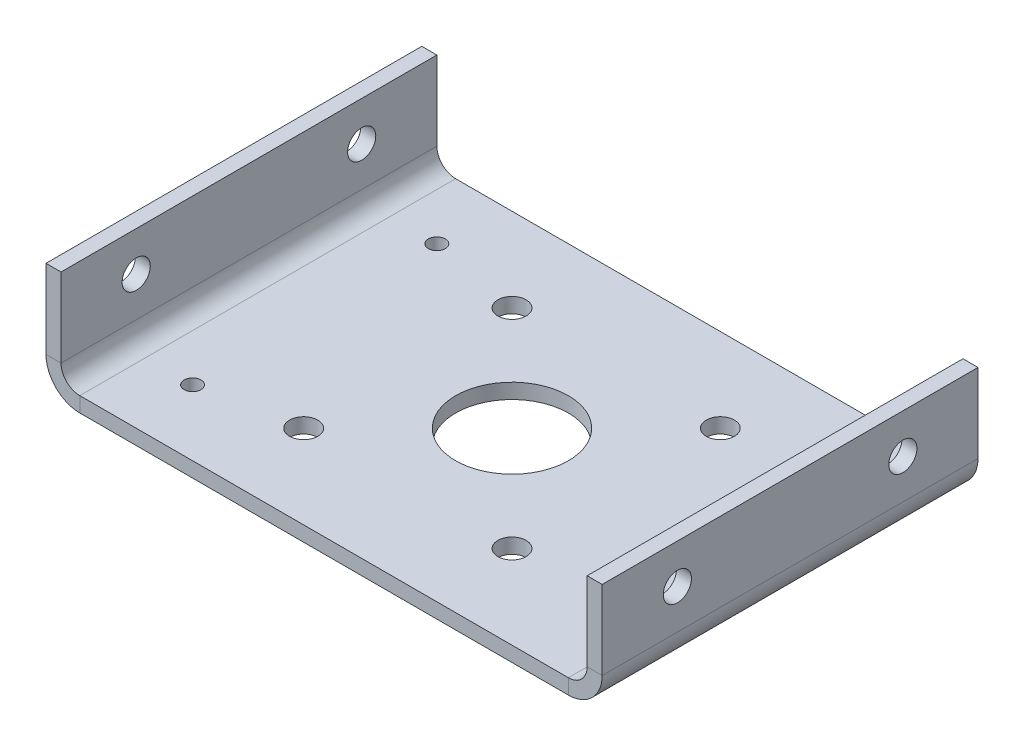
SolidWorks part; units mm, degrees
note: The reader was unsure of these and kept them because the rebuilt part matched: flange length of "Edge-Flange1".
material "Plain Carbon Steel"
ref_plane "Front Plane" through (0, 0, 0) normal (0, 0, 1) x (1, 0, 0)
ref_plane "Top Plane" through (0, 0, 0) normal (0, 1, 0) x (1, 0, 0)
ref_plane "Right Plane" through (0, 0, 0) normal (1, 0, 0) x (0, 0, -1)
sketch "Sketch1" plane through (0, 0, 0) normal (0, 1, 0) x (1, 0, 0)
  line L1 (-148, -100) -> (148, -100)
  line L2 (-148, -100) -> (-148, 100)
  line L3 (-148, 100) -> (148, 100)
  line L4 (148, -100) -> (148, 100)
  line L5 (-148, -100) -> (148, 100) construction
  line L6 (-148, 100) -> (148, -100) construction
  point P0 (0, 0)
  dimension "D1" = 296
  dimension "D2" = 200
base flange "Base-Flange1" sketch "Sketch1" thickness 8 reverse thickness direction no parameters "D1"=3
edge flange "Edge-Flange1" sketch "Sketch10" flange profiles "Sketch10", "Sketch11" flange angle 90 flange length 60 flange position material inside bend radius 10 thickness 8 relief rectangular parameters "D6"=10, "D8"=1
sketch "Sketch10" plane through (-148, 0, 0) normal (-1, 0, 0) x (0, 0, 1)
  line L0 (-100, 0) -> (100, 0) construction
  line L1 (-100, 0) -> (100, 0)
  line L2 (-100, 0) -> (-100, 52)
  line L3 (-100, 52) -> (100, 52)
  line L4 (100, 52) -> (100, 0)
sketch "Sketch11" plane through (148, 0, 0) normal (1, 0, 0) x (0, 0, -1)
  line L0 (-100, 0) -> (100, 0) construction
  line L1 (-100, 0) -> (100, 0)
  line L2 (-100, 0) -> (-100, 52)
  line L3 (-100, 52) -> (100, 52)
  line L4 (100, 52) -> (100, 0)
bend "EdgeBend1" bend radius 10 bend angle 90 parameters "D5"=1
bend "EdgeBend2" bend radius 10 bend angle 90 parameters "D5"=2
sketch "Sketch12" plane through (0, -8, 0) normal (0, -1, 0) x (-1, 0, 0)
  circle A0 centre (0, 0) radius 30
  dimension "D1" = 60
extrude "Cut-Extrude1" cut sketch "Sketch12" against normal blind 10
sketch "Sketch13" plane through (0, -8, 0) normal (0, -1, 0) x (-1, 0, 0)
  line L3 (-55.4372, -55.4372) -> (55.4372, -55.4372) construction
  line L4 (-55.4372, -55.4372) -> (-55.4372, 55.4372) construction
  line L5 (-55.4372, 55.4372) -> (55.4372, 55.4372) construction
  line L6 (55.4372, -55.4372) -> (55.4372, 55.4372) construction
  line L7 (-55.4372, -55.4372) -> (55.4372, 55.4372) construction
  line L8 (-55.4372, 55.4372) -> (55.4372, -55.4372) construction
  circle A0 centre (55.4372, -55.4372) radius 7.5
  point P4 (0, 0)
  dimension "D1" = 15
  dimension "D3" = 78.4
extrude "Cut-Extrude2" cut sketch "Sketch13" against normal blind 10
mirror "Mirror4" about plane through (0, 0, 0) normal (1, 0, 0) of "Cut-Extrude2"
sketch "Sketch15" plane through (-148, 0, 0) normal (-1, 0, 0) x (0, 0, 1)
  line L2 (-100, 0) -> (-100, 52) construction
  line L3 (100, 10) -> (-100, 10) construction
  circle A0 centre (-60, 31) radius 7.5
  dimension "D1" = 15
  dimension "D2" = 40
  dimension "D3" = 21
extrude "Cut-Extrude3" cut sketch "Sketch15" against normal through all
sketch "Sketch16" plane through (0, -8, 0) normal (0, -1, 0) x (-1, 0, 0)
  line L1 (130, -100) -> (130, 100) construction
  line L2 (-130, 100) -> (130, 100) construction
  circle A0 centre (105, 65) radius 4.5
  dimension "D1" = 25
  dimension "D2" = 35
  dimension "D3" = 9
extrude "Cut-Extrude4" cut sketch "Sketch16" against normal blind 10
mirror "Mirror5" about plane through (0, 0, 0) normal (0, 0, 1) of "Cut-Extrude3", "Mirror4", "Cut-Extrude4", "Cut-Extrude2"
sketch "Bend-Lines1" [suppressed] plane through (0, 0, 0) normal (0, 1, 0) x (1, 0, 0)
sketch "Bounding-Box1" [suppressed] plane through (0, 0, 0) normal (0, 1, 0) x (1, 0, 0)
sheet metal parameters "Sheet-Metal1" thickness 8 parameters "D1"=3
flat pattern "Flat-Pattern1" [suppressed]
sketch "Bend-Lines2" plane through (0, 0, 0) normal (0, 1, 0) x (1, 0, 0)
sketch3d "Bounding-Box2" [suppressed]
  line L0 (-100, -100, 0) -> (-100, 100, 0) construction
  line L1 (100, -100, 0) -> (100, 100, 0) construction
  line L2 (-100, -100, 0) -> (100, -100, 0) construction
  line L3 (-100, 100, 0) -> (100, 100, 0) construction
sheet metal parameters "Sheet-Metal2" thickness 8 parameters "D1"=3
flat pattern "Flat-Pattern1"
sketch "Bend-Lines2" plane through (0, 0, 0) normal (0, 1, 0) x (1, 0, 0)
  line L0 (142.9956, -100) -> (142.9956, 100) construction
  line L1 (-142.9956, 100) -> (-142.9956, -100) construction
  line L2 (142.9956, -100) -> (142.9956, 100) construction
  line L3 (-142.9956, 100) -> (-142.9956, -100) construction
sketch3d "Bounding-Box2" [suppressed]
  line L0 (205.9911, 100, 0) -> (-205.9911, 100, 0) construction
  line L1 (205.9911, -100, 0) -> (-205.9911, -100, 0) construction
  line L2 (205.9911, 100, 0) -> (205.9911, -100, 0) construction
  line L3 (-205.9911, 100, 0) -> (-205.9911, -100, 0) construction
bend of the flat pattern "Flatten-<EdgeBend1>1"
bend of the flat pattern "Flatten-<EdgeBend2>1"
sheet metal parameters "Sheet-Metal3" thickness 8 parameters "D1"=3
flat pattern "Flat-Pattern1"
sketch "Bend-Lines2" plane through (0, 0, 0) normal (0, 1, 0) x (1, 0, 0)
  line L0 (142.9956, -100) -> (142.9956, 100) construction
  line L1 (-142.9956, 100) -> (-142.9956, -100) construction
  line L2 (142.9956, -100) -> (142.9956, 100) construction
  line L3 (-142.9956, 100) -> (-142.9956, -100) construction
sketch3d "Bounding-Box2" [suppressed]
  line L0 (205.9911, 100, 0) -> (-205.9911, 100, 0) construction
  line L1 (205.9911, -100, 0) -> (-205.9911, -100, 0) construction
  line L2 (205.9911, 100, 0) -> (205.9911, -100, 0) construction
  line L3 (-205.9911, 100, 0) -> (-205.9911, -100, 0) construction
bend of the flat pattern "Flatten-<EdgeBend1>1"
bend of the flat pattern "Flatten-<EdgeBend2>1"
sheet metal parameters "Sheet-Metal5" thickness 8 parameters "D1"=3
flat pattern "Flat-Pattern1"
sketch "Bend-Lines2" plane through (0, 0, 0) normal (0, 1, 0) x (1, 0, 0)
  line L0 (142.9956, -100) -> (142.9956, 100) construction
  line L1 (-142.9956, 100) -> (-142.9956, -100) construction
  line L2 (142.9956, -100) -> (142.9956, 100) construction
  line L3 (-142.9956, 100) -> (-142.9956, -100) construction
sketch3d "Bounding-Box2" [suppressed]
  line L0 (205.9911, 100, 0) -> (-205.9911, 100, 0) construction
  line L1 (205.9911, -100, 0) -> (-205.9911, -100, 0) construction
  line L2 (205.9911, 100, 0) -> (205.9911, -100, 0) construction
  line L3 (-205.9911, 100, 0) -> (-205.9911, -100, 0) construction
bend of the flat pattern "Flatten-<EdgeBend1>1"
bend of the flat pattern "Flatten-<EdgeBend2>1"
sheet metal parameters "Sheet-Metal7" thickness 8 parameters "D1"=3
flat pattern "Flat-Pattern1"
sketch "Bend-Lines2" plane through (0, 0, 0) normal (0, 1, 0) x (1, 0, 0)
  line L0 (140.9956, -100) -> (140.9956, 100) construction
  line L1 (-140.9956, 100) -> (-140.9956, -100) construction
  line L2 (140.9956, -100) -> (140.9956, 100) construction
  line L3 (-140.9956, 100) -> (-140.9956, -100) construction
sketch3d "Bounding-Box2" [suppressed]
  line L0 (203.9911, 100, 0) -> (-203.9911, 100, 0) construction
  line L1 (203.9911, -100, 0) -> (-203.9911, -100, 0) construction
  line L2 (203.9911, 100, 0) -> (203.9911, -100, 0) construction
  line L3 (-203.9911, 100, 0) -> (-203.9911, -100, 0) construction
bend of the flat pattern "Flatten-<EdgeBend1>1"
bend of the flat pattern "Flatten-<EdgeBend2>1"
sheet metal parameters "Sheet-Metal8" thickness 8 parameters "D1"=3
flat pattern "Flat-Pattern1"
sketch "Bend-Lines2" plane through (0, 0, 0) normal (0, 1, 0) x (1, 0, 0)
  line L0 (140.9956, -100) -> (140.9956, 100) construction
  line L1 (-140.9956, 100) -> (-140.9956, -100) construction
  line L2 (140.9956, -100) -> (140.9956, 100) construction
  line L3 (-140.9956, 100) -> (-140.9956, -100) construction
sketch3d "Bounding-Box2" [suppressed]
  line L0 (193.9911, 100, 0) -> (-193.9911, 100, 0) construction
  line L1 (193.9911, -100, 0) -> (-193.9911, -100, 0) construction
  line L2 (193.9911, 100, 0) -> (193.9911, -100, 0) construction
  line L3 (-193.9911, 100, 0) -> (-193.9911, -100, 0) construction
bend of the flat pattern "Flatten-<EdgeBend1>1"
bend of the flat pattern "Flatten-<EdgeBend2>1"
sheet metal parameters "Sheet-Metal9" thickness 8 parameters "D1"=3
flat pattern "Flat-Pattern1"
sketch "Bend-Lines2" plane through (0, 0, 0) normal (0, 1, 0) x (1, 0, 0)
  line L0 (140.9956, -100) -> (140.9956, 100) construction
  line L1 (-140.9956, 100) -> (-140.9956, -100) construction
  line L2 (140.9956, -100) -> (140.9956, 100) construction
  line L3 (-140.9956, 100) -> (-140.9956, -100) construction
sketch3d "Bounding-Box2" [suppressed]
  line L0 (203.9911, 100, 0) -> (-203.9911, 100, 0) construction
  line L1 (203.9911, -100, 0) -> (-203.9911, -100, 0) construction
  line L2 (203.9911, 100, 0) -> (203.9911, -100, 0) construction
  line L3 (-203.9911, 100, 0) -> (-203.9911, -100, 0) construction
bend of the flat pattern "Flatten-<EdgeBend1>1"
bend of the flat pattern "Flatten-<EdgeBend2>1"
sheet metal parameters "Sheet-Metal10" thickness 8 parameters "D1"=3
flat pattern "Flat-Pattern1"
sketch "Bend-Lines2" plane through (0, 0, 0) normal (0, 1, 0) x (1, 0, 0)
  line L0 (140.9956, -100) -> (140.9956, 100) construction
  line L1 (-140.9956, 100) -> (-140.9956, -100) construction
  line L2 (140.9956, -100) -> (140.9956, 100) construction
  line L3 (-140.9956, 100) -> (-140.9956, -100) construction
sketch3d "Bounding-Box2" [suppressed]
  line L0 (193.9911, 100, 0) -> (-193.9911, 100, 0) construction
  line L1 (193.9911, -100, 0) -> (-193.9911, -100, 0) construction
  line L2 (193.9911, 100, 0) -> (193.9911, -100, 0) construction
  line L3 (-193.9911, 100, 0) -> (-193.9911, -100, 0) construction
bend of the flat pattern "Flatten-<EdgeBend1>1"
bend of the flat pattern "Flatten-<EdgeBend2>1"
